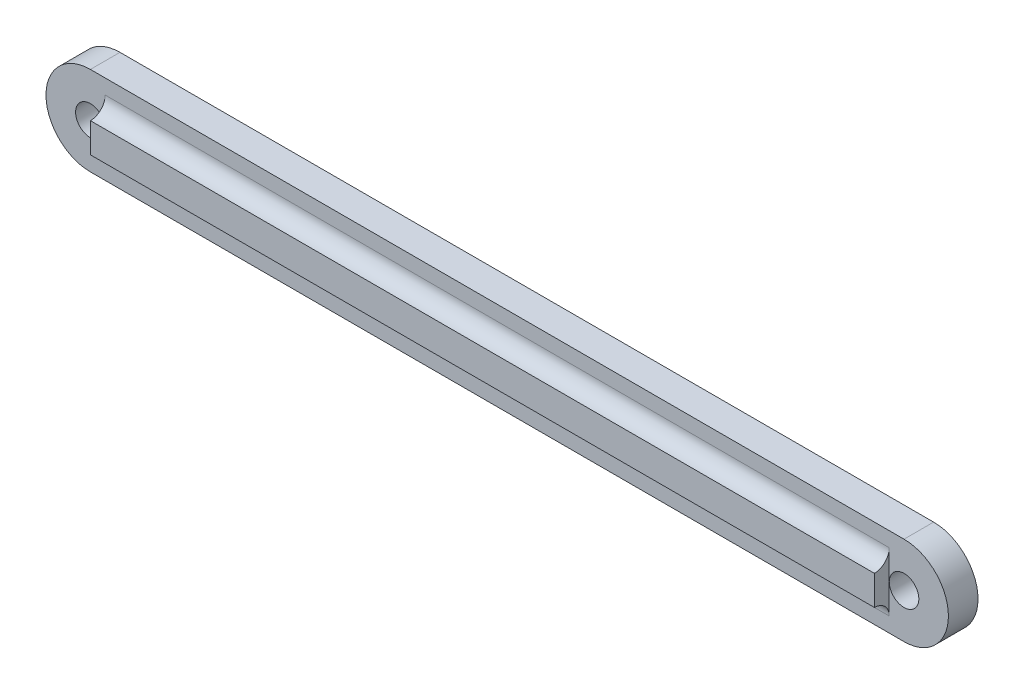
SolidWorks part; units mm, degrees
ref_plane "前视基准面" through (0, 0, 0) normal (0, 0, 1) x (1, 0, 0)
ref_plane "上视基准面" through (0, 0, 0) normal (0, 1, 0) x (1, 0, 0)
ref_plane "右视基准面" through (0, 0, 0) normal (1, 0, 0) x (0, 0, -1)
other "Configuration Table"
sketch "草图1" plane through (0, 0, 0) normal (0, 0, 1) x (1, 0, 0)
  line L0 (-1000, 0) -> (0, 0) construction
  line L2 (0, 1.5) -> (27.5, 1.5)
  line L3 (0, -1.5) -> (27.5, -1.5)
  line L4 (29, 0) -> (49000, 0) construction
  arc A0 (0, 1.5) -> (0, -1.5) centre (0, 0) ccw
  arc A1 (27.5, -1.5) -> (27.5, 1.5) centre (27.5, 0) ccw
  circle A2 centre (0, 0) radius 0.5
  circle A3 centre (27.5, 0) radius 0.5
  dimension "D1" = 3
  dimension "D3" = 1.5
  dimension "D4" = 1
  dimension "D5" = 1
  dimension "D2" = 27.5
extrude "凸台-拉伸1" add sketch "草图1" along normal blind 1
sketch "草图2" plane through (0, 0, 1) normal (0, 0, 1) x (1, 0, 0)
  line L0 (0.5, 0.5) -> (27, 0.5)
  line L1 (27, -0.5) -> (0.5, -0.5)
  line L2 (0.5, 0.5) -> (0.5, -0.5)
  line L3 (27, 0.5) -> (27, -0.5)
extrude "凸台-拉伸2" add sketch "草图2" along normal blind 0.5
fillet "圆角4" radius 0.5 2 edges at (13.75, -0.5, 1) (13.75, 0.5, 1)
sketch "草图3" plane through (0, 0, 0) normal (0, 0, -1) x (-1, 0, 0)
  line L1 (-27, 0.5) -> (-0.5, 0.5)
  line L2 (-27, 0.5) -> (-27, -0.5)
  line L3 (-27, -0.5) -> (-0.5, -0.5)
  line L4 (-0.5, 0.5) -> (-0.5, -0.5)
  circle A0 centre (-27.5, 0) radius 0.5 construction
  circle A1 centre (0, 0) radius 0.5 construction
extrude "凸台-拉伸3" add sketch "草图3" along normal blind 0.5
fillet "圆角6" radius 0.5 2 edges at (13.75, -0.5, 0) (13.75, 0.5, 0)
